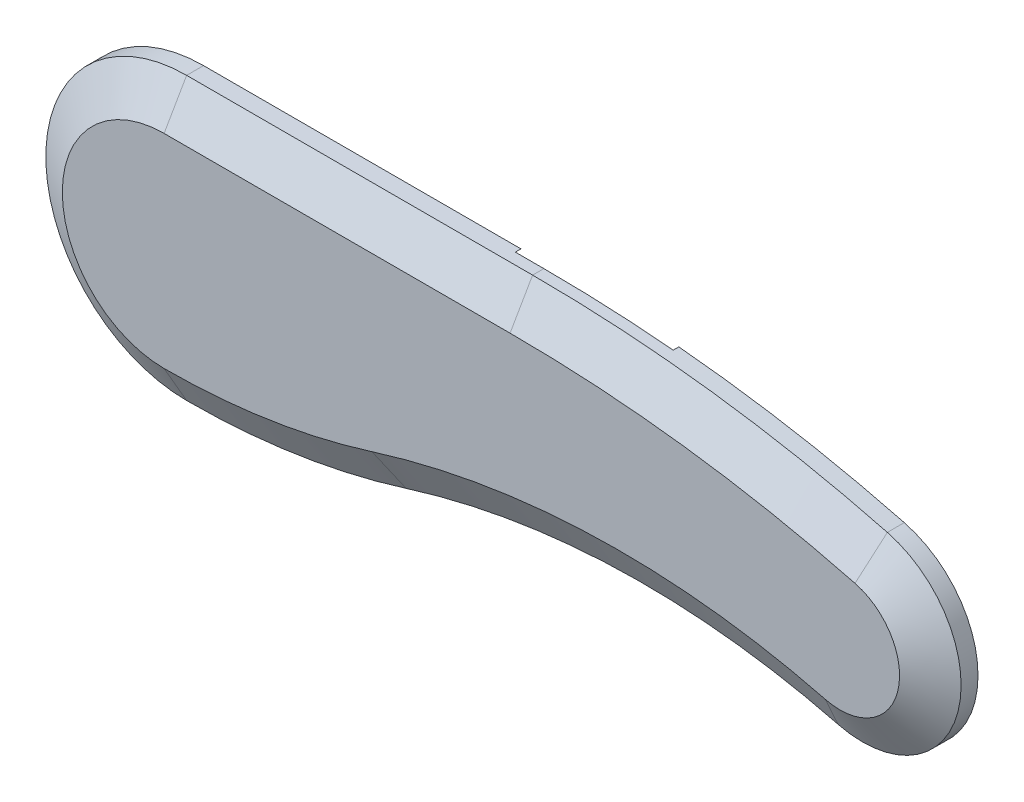
SolidWorks part; units mm, degrees
ref_plane "Front Plane" through (0, 0, 0) normal (0, 0, 1) x (1, 0, 0)
ref_plane "Top Plane" through (0, 0, 0) normal (0, 1, 0) x (1, 0, 0)
ref_plane "Right Plane" through (0, 0, 0) normal (1, 0, 0) x (0, 0, -1)
sketch "Sketch1" plane through (0, 0, 0) normal (0, 0, 1) x (1, 0, 0)
  line L0 (0, 0) -> (120, 0) construction
  line L1 (0, 0) -> (0, -25) construction
  line L2 (0, 25) -> (61.4231, 25)
  circle A0 centre (0, 0) radius 25
  circle A2 centre (120, 0) radius 17.5
  arc A3 (61.4231, 25) -> (124.409, 16.9355) centre (61.4231, -225) cw
  arc A4 (0, -25) -> (38.9734, -19.0205) centre (0, 105) ccw
  arc A5 (38.9734, -19.0205) -> (115.6605, -16.9534) centre (80.9448, -152.5809) cw
  dimension "D2" = 50
  dimension "D4" = 35
  dimension "D5" = 250
  dimension "D6" = 140
  dimension "D7" = 130
  dimension "D1" = 120
  dimension "D3" = 0
extrude "Boss-Extrude1" add sketch "Sketch1" along normal blind 7 contours A0 L0 A2 A3 L2 | L0 A0 A4 A5 A2 | A0 | A2 region at (60.7118, 4.4003, 0) region at (0, 0, 0) region at (120, 0, 0)
chamfer "Chamfer1" distance 4 angle 60 6 edges at (19.7147, -23.4964, 7) (-25, 0, 7) (30.7116, 25, 7) (93.1732, 22.9757, 7) (136.9445, -4.3742, 7) (77.1726, -12.6318, 7) first distance on face at (19.6007, -22.7533, 3.5) first distance on face at (-12.5, 0, 3.5) first distance on face at (30.7116, 25, 3.5) first distance on face at (93.0446, 21.9717, 3.5) first distance on face at (128.4896, -2.1916, 3.5) first distance on face at (77.2448, -15.3094, 3.5)
sketch "Sketch3" plane through (0, 0, 0) normal (0, 0, -1) x (-1, 0, 0)
  circle A0 centre (0, 0) radius 8.5
  circle A1 centre (-120, 0) radius 8.5
  dimension "D1" = 17
  dimension "D2" = 17
extrude "Cut-Extrude2" cut sketch "Sketch3" against normal blind 4
ref_plane "Plane1" through (0, 0, 2) normal (0, 0, -1) x (-1, 0, 0)
sketch "Sketch5" plane through (0, 0, 2) normal (0, 0, -1) x (-1, 0, 0)
  line L0 (0, 0) -> (-60, 0) construction
  line L1 (0, 0) -> (-83.9535, 13.2969) construction
  line L2 (0, 0) -> (-30.0702, -10.9446) construction
  line L3 (-86.0464, 16.9219) -> (-73.7677, 16.9219)
  line L4 (-81.8606, 9.6719) -> (-79.7677, 13.2969)
  line L5 (-79.7677, 13.2969) -> (-81.8606, 16.9219)
  line L6 (-81.8606, 16.9219) -> (-86.0464, 16.9219)
  line L7 (-86.0464, 16.9219) -> (-88.1393, 13.2969)
  line L8 (-88.1393, 13.2969) -> (-86.0464, 9.6719)
  line L9 (-86.0464, 9.6719) -> (-81.8606, 9.6719)
  line L10 (-57.9071, -3.625) -> (-55.8142, 0)
  line L11 (-55.8142, 0) -> (-57.9071, 3.625)
  line L12 (-57.9071, 3.625) -> (-62.0929, 3.625)
  line L13 (-62.0929, 3.625) -> (-64.1858, 0)
  line L14 (-64.1858, 0) -> (-62.0929, -3.625)
  line L15 (-62.0929, -3.625) -> (-57.9071, -3.625)
  line L16 (-27.9773, -14.5696) -> (-25.8844, -10.9446)
  line L17 (-25.8844, -10.9446) -> (-27.9773, -7.3196)
  line L18 (-27.9773, -7.3196) -> (-32.1631, -7.3196)
  line L19 (-32.1631, -7.3196) -> (-34.256, -10.9446)
  line L20 (-34.256, -10.9446) -> (-32.1631, -14.5696)
  line L21 (-32.1631, -14.5696) -> (-27.9773, -14.5696)
  line L22 (-86.0464, 9.6719) -> (-73.7677, 9.6719)
  line L23 (-73.7677, 16.9219) -> (-73.7677, 9.6719) construction
  line L24 (-62.0929, 3.625) -> (-49.8142, 3.625)
  line L25 (-62.0929, -3.625) -> (-49.8142, -3.625)
  line L26 (-49.8142, 3.625) -> (-49.8142, -3.625) construction
  line L27 (-32.1631, -7.3196) -> (-19.8844, -7.3196)
  line L28 (-32.1631, -14.5696) -> (-19.8844, -14.5696)
  line L29 (-19.8844, -14.5696) -> (-19.8844, -7.3196) construction
  circle A0 centre (-83.9535, 13.2969) radius 3.625 construction
  circle A1 centre (-60, 0) radius 3.625 construction
  circle A2 centre (-30.0702, -10.9446) radius 3.625 construction
  circle A3 centre (-73.7677, 13.2969) radius 6
  circle A4 centre (-49.8142, 0) radius 6
  circle A5 centre (-19.8844, -10.9446) radius 6
  circle A6 centre (-83.9535, 13.2969) radius 2.125
  circle A7 centre (-60, 0) radius 2.125
  circle A8 centre (-30.0702, -10.9446) radius 2.125
  dimension "D7" = 12
  dimension "D8" = 4.25
  dimension "D1" = 20
  dimension "D2" = 9
  dimension "D3" = 85
  dimension "D4" = 60
  dimension "D5" = 32
  dimension "D6" = 7.25
extrude "Cut-Extrude3" cut sketch "Sketch5" against normal blind 3.5 contours L8 L9 L4 L5 L3 L7 | A3 | A3 L3 L5 | A3 L4 L22 | L14 L15 L10 L11 L12 L13 | A4 L24 L11 | A4 L10 L25 | A4 | A5 | A5 L16 L28 | A5 L27 L17 | L20 L21 L16 L17 L18 L19 | A7 | A8 | A6 region at (83.9535, 16.8112, 2) region at (80.1796, 15.8006, 2) region at (73.7677, 13.2969, 2) region at (80.1796, 10.7933, 2) region at (60, -3.5143, 2) region at (56.2261, -2.5037, 2) region at (56.2261, 2.5037, 2) region at (49.8142, 0, 2) region at (30.0702, -14.4589, 2) region at (26.2963, -13.4483, 2) region at (26.2963, -8.441, 2) region at (19.8844, -10.9446, 2) region at (60, 0, 2) region at (30.0702, -10.9446, 2)
extrude "Cut-Extrude4" cut sketch "Sketch5<3>" along normal through all contours A3 | A4 | A5 | A6 | A7 | A8 region at (73.7677, 13.2969, 2) region at (49.8142, 0, 2) region at (19.8844, -10.9446, 2) region at (83.9535, 13.2969, 2) region at (60, 0, 2) region at (30.0702, -10.9446, 2)
sketch "Sketch5<3>" plane through (0, 0, 2) normal (0, 0, -1) x (-1, 0, 0) same geometry as "Sketch5"
chamfer "Chamfer2" distance 0.5 angle 70 3 edges at (67.7677, 13.2969, 5.5) (13.8844, -10.9446, 5.5) (43.8142, 0, 5.5) first distance on face at (76.1583, 13.2969, 3.75) first distance on face at (22.2749, -10.9446, 3.75) first distance on face at (52.2048, 0, 3.75)
sketch "Sketch7" plane through (0, 0, 0) normal (0, 0, -1) x (-1, 0, 0)
  circle A0 centre (0, 0) radius 9.5
  circle A1 centre (0, 0) radius 8.5 construction
  circle A2 centre (0, 0) radius 8.5
  circle A3 centre (-120, 0) radius 8.5 construction
  circle A4 centre (-120, 0) radius 8.5
  circle A5 centre (-120, 0) radius 9.5
  dimension "D1" = 1
  dimension "D2" = 1
extrude "Boss-Extrude2" add sketch "Sketch7" along normal blind 0.5
sketch "Sketch8" plane through (0, 0, 0) normal (0, 0, -1) x (-1, 0, 0)
  line L0 (-91.0061, -1.4841) -> (-79.8556, -10.8405) construction
  line L1 (-13.4637, -10.2418) -> (-53.2327, 23.1284) construction
  line L2 (-58.375, 25) -> (-61.4231, 25) construction
  line L3 (-93.3813, 7.3804) -> (-89.1932, 18.8872) construction
  line L4 (-91.0061, -1.4841) -> (-79.8556, -10.8405)
  line L5 (-13.4637, -10.2418) -> (-53.2327, 23.1284)
  line L6 (-58.375, 25) -> (-61.4231, 25)
  line L7 (-93.3813, 7.3804) -> (-89.1932, 18.8872)
  line L8 (-91.1668, -1.6756) -> (-80.0163, -11.032)
  line L9 (-93.6163, 7.4659) -> (-89.4281, 18.9727)
  line L10 (-58.375, 25.25) -> (-61.4231, 25.25)
  line L11 (-13.303, -10.0503) -> (-53.072, 23.3199)
  arc A0 (-10.6159, -15.9715) -> (-13.4637, -10.2418) centre (-18.606, -16.3702) ccw construction
  arc A1 (-19.8261, -23.4793) -> (-10.6159, -15.9715) centre (-18.606, -15.5729) ccw construction
  arc A2 (-38.9734, -19.0205) -> (-19.8261, -23.4793) centre (0, 105) ccw construction
  arc A3 (-38.9734, -19.0205) -> (-75.0501, -12.7051) centre (-80.9448, -152.5809) ccw construction
  arc A4 (-79.8556, -10.8405) -> (-75.0501, -12.7051) centre (-74.7133, -4.7122) ccw construction
  arc A5 (-93.3813, 7.3804) -> (-91.0061, -1.4841) centre (-85.8638, 4.6442) ccw construction
  arc A6 (-53.2327, 23.1284) -> (-58.375, 25) centre (-58.375, 17) ccw construction
  arc A7 (-82.3452, 24.123) -> (-89.1932, 18.8872) centre (-81.6757, 16.1511) ccw construction
  arc A8 (-61.4231, 25) -> (-82.3452, 24.123) centre (-61.4231, -225) ccw construction
  arc A9 (-10.6159, -15.9715) -> (-13.4637, -10.2418) centre (-18.606, -16.3702) ccw
  arc A10 (-19.8261, -23.4793) -> (-10.6159, -15.9715) centre (-18.606, -15.5729) ccw
  arc A11 (-38.9734, -19.0205) -> (-19.8261, -23.4793) centre (0, 105) ccw
  arc A12 (-38.9734, -19.0205) -> (-75.0501, -12.7051) centre (-80.9448, -152.5809) ccw
  arc A13 (-79.8556, -10.8405) -> (-75.0501, -12.7051) centre (-74.7133, -4.7122) ccw
  arc A14 (-93.3813, 7.3804) -> (-91.0061, -1.4841) centre (-85.8638, 4.6442) ccw
  arc A15 (-53.2327, 23.1284) -> (-58.375, 25) centre (-58.375, 17) ccw
  arc A16 (-82.3452, 24.123) -> (-89.1932, 18.8872) centre (-81.6757, 16.1511) ccw
  arc A17 (-61.4231, 25) -> (-82.3452, 24.123) centre (-61.4231, -225) ccw
  arc A18 (-39.0484, -19.259) -> (-75.0606, -12.9549) centre (-80.9448, -152.5809) ccw
  arc A19 (-80.0163, -11.032) -> (-75.0606, -12.9549) centre (-74.7133, -4.7122) ccw
  arc A20 (-93.6163, 7.4659) -> (-91.1668, -1.6756) centre (-85.8638, 4.6442) ccw
  arc A21 (-82.3661, 24.3721) -> (-89.4281, 18.9727) centre (-81.6757, 16.1511) ccw
  arc A22 (-61.4231, 25.25) -> (-82.3661, 24.3721) centre (-61.4231, -225) ccw
  arc A23 (-53.072, 23.3199) -> (-58.375, 25.25) centre (-58.375, 17) ccw
  arc A24 (-10.3656, -15.9715) -> (-13.303, -10.0503) centre (-18.606, -16.3702) ccw
  arc A25 (-19.8642, -23.7264) -> (-10.3656, -15.9715) centre (-18.606, -15.5729) ccw
  arc A26 (-39.0484, -19.259) -> (-19.8642, -23.7264) centre (0, 105) ccw
  circle M16 centre (-19.8844, -10.9446) radius 6
  arc M21 (-38.9734, -19.0205) -> (0, -25) centre (0, 105) ccw
  line M23 (0, 25) -> (-61.4231, 25)
  arc M24 (-61.4231, 25) -> (-124.409, 16.9355) centre (-61.4231, -225) ccw
  arc M26 (-115.6605, -16.9534) -> (-38.9734, -19.0205) centre (-80.9448, -152.5809) cw
  dimension "D1" = 0.25
extrude "Cut-Extrude5" cut sketch "Sketch8" against normal blind 1 contours A23 L10 A22 A21 M23 M24 | L11 A23 A15 L5 M23 M16 | L11 L5 M16 | A25 A24 L11 L5 A9 A10 M21 M16 | A18 A26 A25 A19 M21 M26 | A21 L9 A20 L8 A19 A13 L4 A14 L7 A16 M24 M26 | A13 A12 A11 A10 A9 L5 A15 L6 A17 A16 L7 A14 L4 region at (85.4575, -6.1941, 0) region at (56.8148, -14.7373, 0) region at (70.3826, 24.8447, 0) region at (13.4425, -21.9072, 0) region at (38.0386, 10.4957, 0) region at (16.8063, -7.2764, 0)
